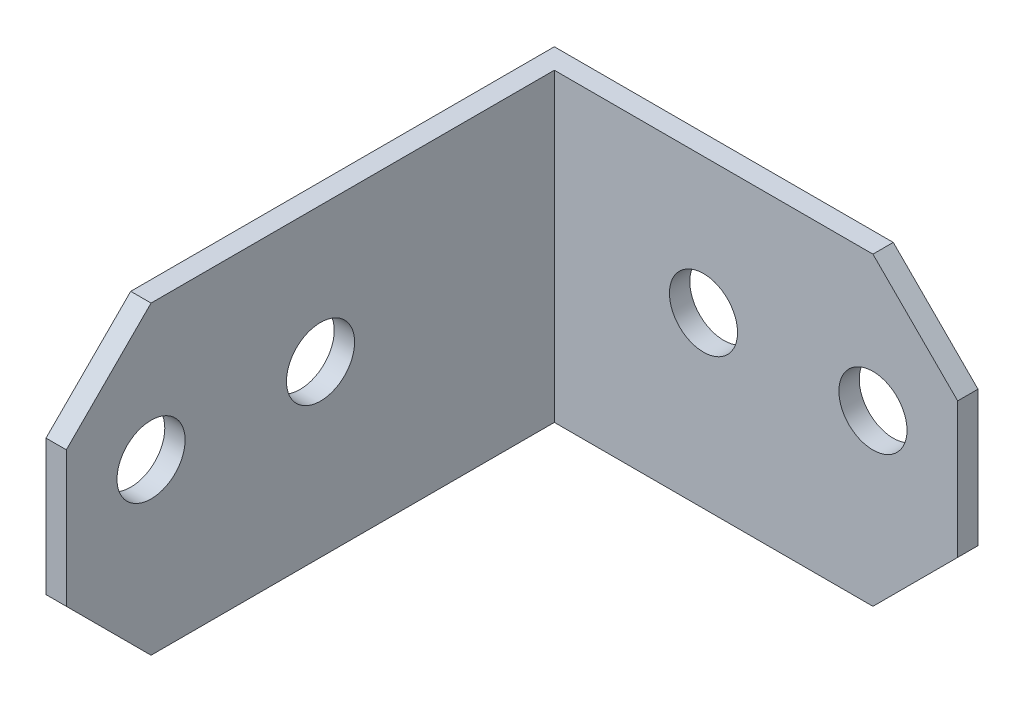
SolidWorks part; units mm, degrees
ref_plane "Front Plane" through (0, 0, 0) normal (0, 0, 1) x (1, 0, 0)
ref_plane "Top Plane" through (0, 0, 0) normal (0, 1, 0) x (1, 0, 0)
ref_plane "Right Plane" through (0, 0, 0) normal (1, 0, 0) x (0, 0, -1)
sketch "Sketch1" plane through (0, 0, 0) normal (0, 1, 0) x (1, 0, 0)
  line L0 (0, 0) -> (0, 38.1)
  line L1 (0, 38.1) -> (31.75, 38.1)
  line L2 (31.75, 38.1) -> (31.75, 36.576)
  line L3 (31.75, 36.576) -> (1.524, 36.576)
  line L4 (1.524, 36.576) -> (1.524, 0)
  line L5 (1.524, 0) -> (0, 0)
  dimension "D1" = 31.75
  dimension "D2" = 38.1
  dimension "D3" = 1.524
  dimension "D4" = 1.524
extrude "Boss-Extrude1" add sketch "Sketch1" along normal blind 22.86
sketch "Sketch2" plane through (1.524, 0, 0) normal (1, 0, 0) x (0, 0, -1)
  line L0 (0, 22.86) -> (36.576, 22.86) construction
  line L1 (38.1, 22.86) -> (38.1, 0) construction
  circle A0 centre (6.35, 12.7) radius 2.5527
  circle A1 centre (19.05, 12.7) radius 2.5527
  dimension "D1" = 5.1054
  dimension "D2" = 5.1054
  dimension "D3" = 10.16
  dimension "D4" = 12.7
  dimension "D5" = 10.16
  dimension "D6" = 19.05
sketch "Sketch3" plane through (0, 0, -36.576) normal (0, 0, 1) x (1, 0, 0)
  line L0 (1.524, 22.86) -> (31.75, 22.86) construction
  line L1 (0, 22.86) -> (0, 0) construction
  circle A0 centre (25.4, 12.7) radius 2.5527
  circle A1 centre (12.7, 12.7) radius 2.5527
  dimension "D1" = 5.1054
  dimension "D2" = 5.1054
  dimension "D3" = 10.16
  dimension "D4" = 10.16
  dimension "D5" = 12.7
  dimension "D6" = 12.7
extrude "Cut-Extrude1" cut sketch "Sketch2" against normal through all
extrude "Cut-Extrude2" cut sketch "Sketch3" against normal through all
chamfer "Chamfer1" distance 6.35 angle 45 4 edges at (0.762, 0, 0) (31.75, 0, -37.338) (0.762, 22.86, 0) (31.75, 22.86, -37.338)
